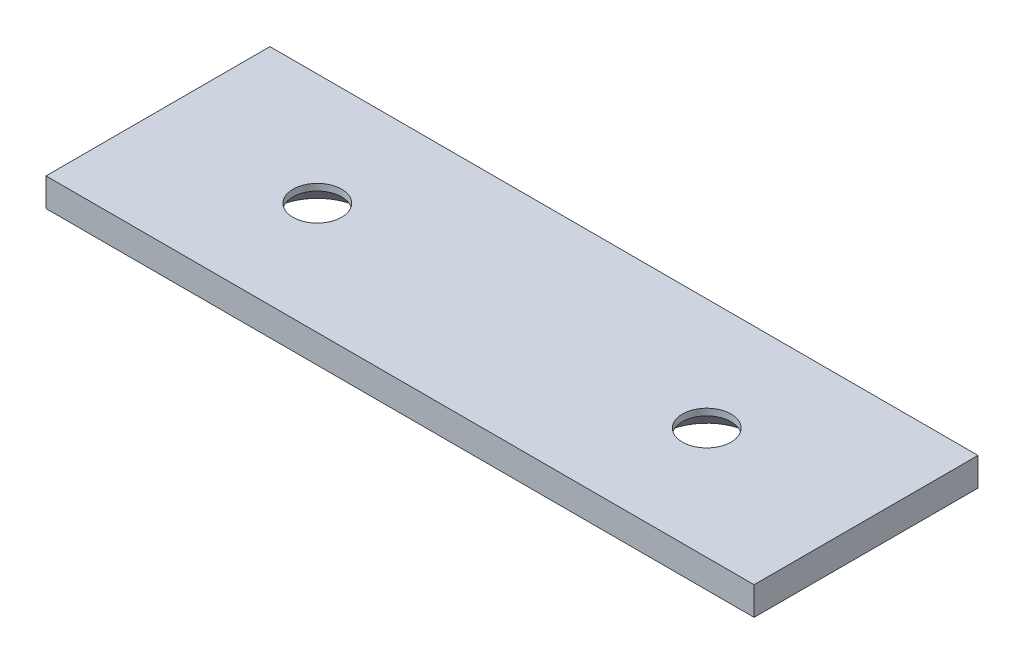
SolidWorks part; units mm, degrees
ref_plane "Front Plane" through (0, 0, 0) normal (0, 0, 1) x (1, 0, 0)
ref_plane "Top Plane" through (0, 0, 0) normal (0, 1, 0) x (1, 0, 0)
ref_plane "Right Plane" through (0, 0, 0) normal (1, 0, 0) x (0, 0, -1)
sketch "Sketch1" plane through (0, 0, 0) normal (0, 1, 0) x (1, 0, 0)
  line L1 (0, 0) -> (80, 0)
  line L2 (0, 0) -> (0, -25.3)
  line L3 (0, -25.3) -> (80, -25.3)
  line L4 (80, 0) -> (80, -25.3)
  dimension "D1" = 80
  dimension "D2" = 25.3
extrude "Boss-Extrude1" add sketch "Sketch1" along normal blind 3.2
hole_wizard "CSK for M5 Flat Head Machine Screw1" positions "Sketch2" profile "Sketch3" countersink size "M5" standard "ANSI Metric" end condition up to next
sketch "Sketch2" plane through (0, 0, 0) normal (0, -1, 0) x (-1, 0, 0)
  point P0 (-62, -12.65)
  point P3 (-18, -12.65)
  point P7 (0, 0)
  point P8 (0, 0)
sketch "Sketch3" plane through (62, 0, 12.65) normal (1, 0, 0) x (0, 0, -1)
  line L0 (0, 0) -> (0, 3.2)
  line L1 (0, 3.2) -> (2.75, 3.2)
  line L2 (2.75, 3.2) -> (2.75, 2.45)
  line L3 (2.75, 2.45) -> (5.2, 0)
  line L5 (5.2, 0) -> (0, 0)
  line L6 (-2.75, 2.45) -> (-5.2, 0) construction
  line L11 (0, -6.35) -> (0, 107.95) construction
  dimension "Thru Hole Dia." = 5.5
  dimension "Thru Hole Depth" = 3.2
  dimension "Near C'Sink Dia." = 10.4
  dimension "Near C'Sink Angle" = 90
